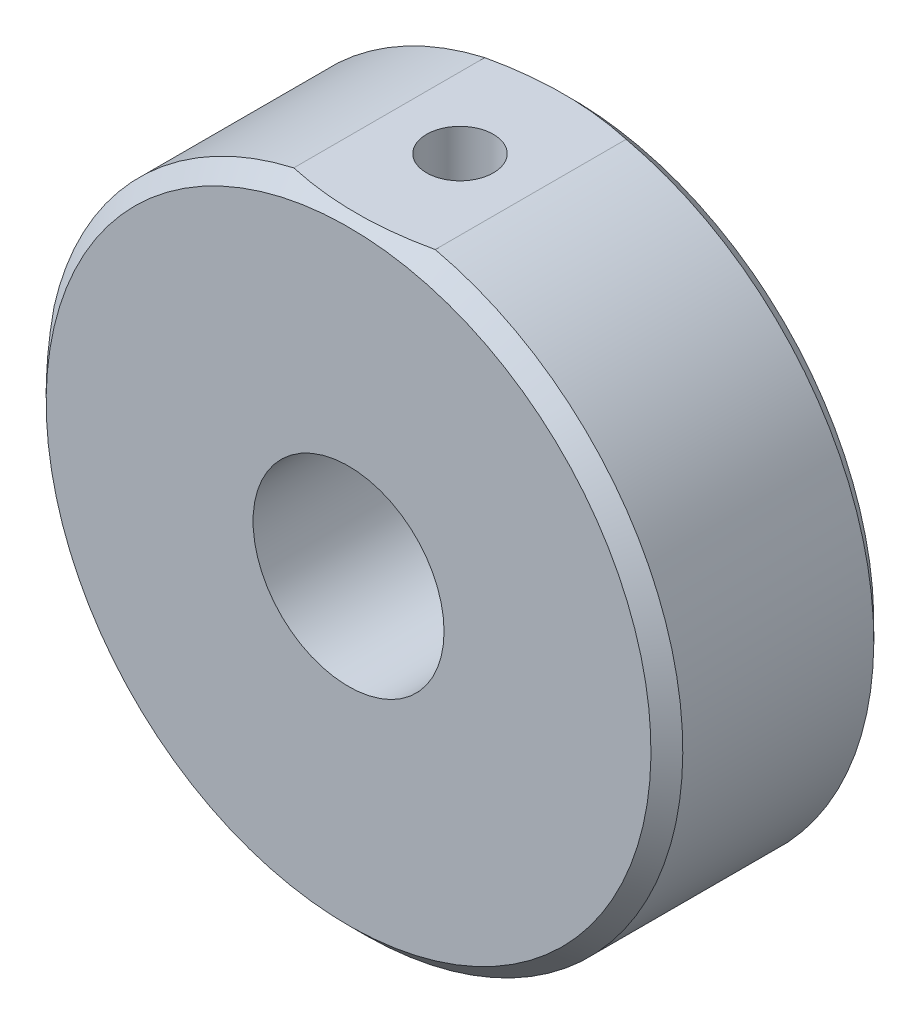
SolidWorks part; units mm, degrees
ref_plane "Front Plane" through (0, 0, 0) normal (0, 0, 1) x (1, 0, 0)
ref_plane "Top Plane" through (0, 0, 0) normal (0, 1, 0) x (1, 0, 0)
ref_plane "Right Plane" through (0, 0, 0) normal (1, 0, 0) x (0, 0, -1)
sketch "Sketch1" plane through (0, 0, 0) normal (0, 0, 1) x (1, 0, 0)
  line L3 (-4.4441, 19.5) -> (4.4441, 19.5)
  line L10 (-19.5, -4.4441) -> (-19.5, 4.4441)
  arc A0 (-19.5, -4.4441) -> (4.4441, 19.5) centre (0, 0) ccw
  arc A1 (-4.4441, 19.5) -> (-19.5, 4.4441) centre (0, 0) ccw
  circle A2 centre (0, 0) radius 6
  point P3 (0, 20)
  point P8 (-20, 0)
  dimension "D1" = 40
  dimension "D2" = 0.5
  dimension "D3" = 0.5
extrude "Boss-Extrude1" add sketch "Sketch1" along normal blind 14
hole_wizard "M5 Tapped Hole1" positions "Sketch2" profile "Sketch3" tap size "M5" standard "ISO"
sketch "Sketch2" plane through (0, 19.5, 0) normal (0, 1, 0) x (1, 0, 0)
  point P0 (0, -7)
sketch "Sketch3" plane through (0, 19.5, 7) normal (1, 0, 0) x (0, 0, 1)
  line L0 (0, 0) -> (0, 13.5)
  line L1 (0, 13.5) -> (2.1, 13.5)
  line L2 (2.1, 13.5) -> (2.1, 0)
  line L5 (2.1, 0) -> (0, 0)
  line L11 (0, -6.35) -> (0, 107.95) construction
  dimension "Thru Tap Drill Dia." = 4.2
  dimension "Thru Tap Drill Depth" = 13.5
cosmetic thread "Hole Thread1" parameters "D2"=5
chamfer "Chamfer1" distance 1 angle 45 2 edges at (-14.1421, 14.1421, 14) (-14.1421, 14.1421, 0)
